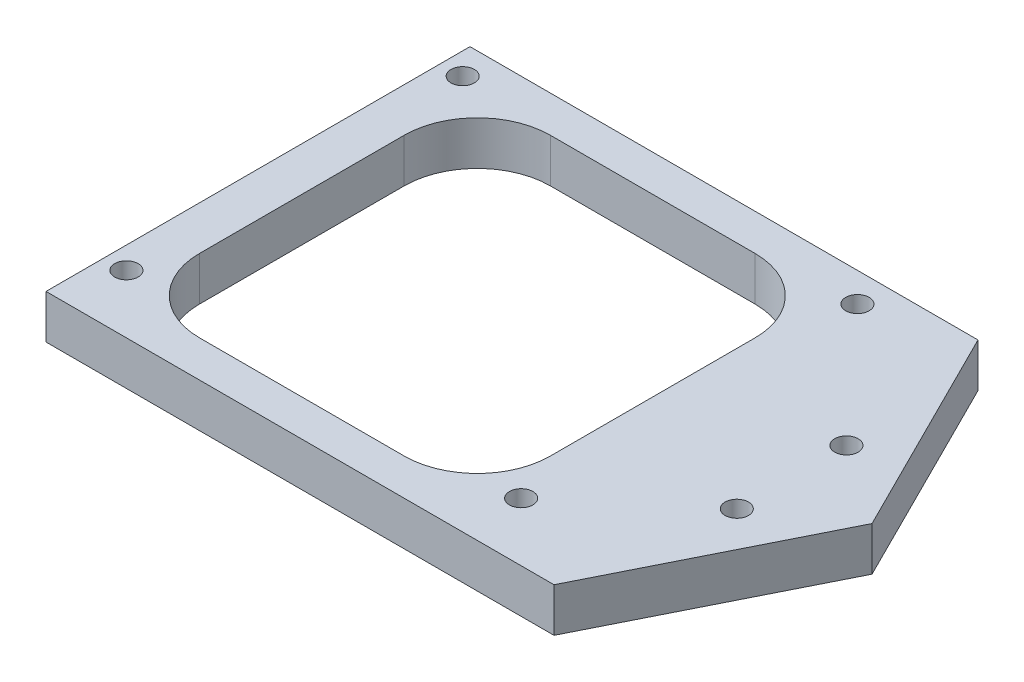
SolidWorks part; units mm, degrees
ref_plane "Front Plane" through (0, 0, 0) normal (0, 0, 1) x (1, 0, 0)
ref_plane "Top Plane" through (0, 0, 0) normal (0, 1, 0) x (1, 0, 0)
ref_plane "Right Plane" through (0, 0, 0) normal (1, 0, 0) x (0, 0, -1)
sketch "Sketch1" plane through (0, 0, 0) normal (0, 1, 0) x (1, 0, 0)
  line L0 (0, 14.5) -> (42, 14.5) construction
  line L1 (0, 0) -> (34.7484, 0)
  line L2 (0, 0) -> (0, 29)
  line L5 (42, 14.5) -> (34.7484, 29)
  line L6 (42, 14.5) -> (34.7484, 0)
  line L7 (0, 29) -> (34.7484, 29)
  dimension "D1" = 29
  dimension "D2" = 42
  dimension "D3" = 63.43
extrude "Boss-Extrude1" add sketch "Sketch1" along normal mid plane 3
sketch "Sketch2" plane through (0, 0, 0) normal (0, 1, 0) x (1, 0, 0)
  line L0 (0, 29) -> (0, 0) construction
  line L1 (3, 26.5) -> (27, 26.5)
  line L2 (3, 26.5) -> (3, 2.5)
  line L4 (27, 26.5) -> (27, 2.5)
  line L5 (0, 14.5) -> (42, 14.5) construction
  line L6 (34.7484, 29) -> (0, 29) construction
  line L7 (3, 2.5) -> (27, 2.5)
  point P9 (27, 14.5)
  point P10 (3, 14.5)
  point P14 (27, 14.5)
  point P15 (3, 14.5)
  dimension "D1" = 3
  dimension "D2" = 24
  dimension "D3" = 2.5
extrude "Cut-Extrude1" cut sketch "Sketch2" against normal through all both and the other way through all
fillet "Fillet1" radius 5 4 edges at (3, 0, -26.5) (27, 0, -26.5) (27, 0, -2.5) (3, 0, -2.5)
sketch "Sketch5" plane through (0, 1.5, 0) normal (0, 1, 0) x (1, 0, 0)
  line L0 (1.5, 27) -> (28.5, 27) construction
  line L1 (28.5, 27) -> (28.5, 4) construction
  line L2 (28.5, 4) -> (1.5, 4) construction
  line L3 (1.5, 4) -> (1.5, 27) construction
  line L4 (34.7484, 29) -> (34.7484, 0) construction
  line L5 (36.4984, 29) -> (36.4984, 0) construction
  line L6 (36.4984, 14.5) -> (34.7484, 14.5) construction
  line L7 (34.7484, 29) -> (0, 29) construction
  line L8 (0, 29) -> (0, 0) construction
  point P16 (36.4984, 18.25)
  point P17 (0, 0)
  point P18 (36.4984, 10.75)
  dimension "D1" = 1.75
  dimension "D2" = 2
  dimension "D3" = 1.5
  dimension "D4" = 23
  dimension "D5" = 27
  dimension "D6" = 3.75
hole_wizard "M2x0.4 Tapped Hole1" positions "3DSketch4" profile "Sketch8" tap size "M2x0.4" standard "ANSI Metric" end condition through all
sketch3d "3DSketch4"
  point P0 (1.5, 1.5, -27)
  point P3 (28.5, 1.5, -27)
  point P6 (36.4984, 1.5, -18.25)
  point P9 (36.4984, 1.5, -10.75)
  point P12 (28.5, 1.5, -4)
  point P15 (1.5, 1.5, -4)
sketch "Sketch8" plane through (1.5, 1.5, -27) normal (1, 0, 0) x (0, 0, 1)
  line L0 (0, 0) -> (0, 3)
  line L1 (0, 3) -> (0.8, 3)
  line L2 (0.8, 3) -> (0.8, 0)
  line L5 (0.8, 0) -> (0, 0)
  line L11 (0, -6.35) -> (0, 107.95) construction
  dimension "Thru Tap Drill Dia." = 1.6
  dimension "Thru Tap Drill Depth" = 3
cosmetic thread "Hole Thread1" parameters "D2"=2
cosmetic thread "Hole Thread2" parameters "D2"=2
cosmetic thread "Hole Thread3" parameters "D2"=2
cosmetic thread "Hole Thread4" parameters "D2"=2
cosmetic thread "Hole Thread5" parameters "D2"=2
cosmetic thread "Hole Thread6" parameters "D2"=2
